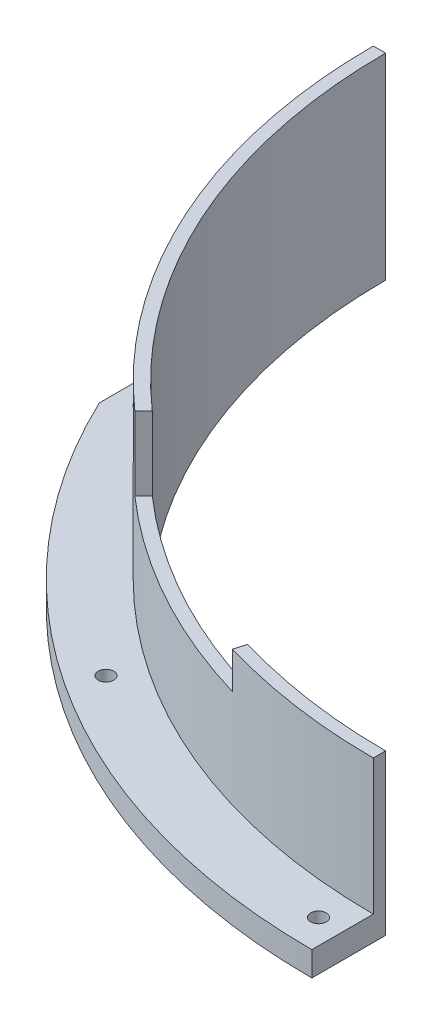
SolidWorks part; units mm, degrees
material "PET"
ref_plane "Front" through (0, 0, 0) normal (0, 0, 1) x (1, 0, 0)
ref_plane "Top" through (0, 0, 0) normal (0, 1, 0) x (1, 0, 0)
ref_plane "Right" through (0, 0, 0) normal (1, 0, 0) x (0, 0, -1)
sketch "Sketch1" plane through (0, 0, 0) normal (0, 1, 0) x (1, 0, 0)
  line L0 (165.608, 0) -> (146.558, 0)
  line L1 (0, -165.608) -> (0, -146.558)
  arc A0 (0, -165.608) -> (165.608, 0) centre (0, 0) ccw
  arc A1 (0, -146.558) -> (146.558, 0) centre (0, 0) ccw
  dimension "D1" = 146.558
  dimension "D2" = 19.05
extrude "Boss-Extrude1" add sketch "Sketch1" along normal blind 6.35
sketch "Sketch2" plane through (0, 6.35, 0) normal (0, 1, 0) x (1, 0, 0)
  line L0 (165.608, 0) -> (146.558, 0) construction
  line L2 (146.558, 0) -> (149.733, 0)
  line L3 (0, -146.558) -> (0, -149.733)
  arc A0 (0, -146.558) -> (146.558, 0) centre (0, 0) ccw
  arc A1 (0, -149.733) -> (149.733, 0) centre (0, 0) ccw
  dimension "D1" = 3.175
extrude "Boss-Extrude2" add sketch "Sketch2" along normal blind 44.45
sketch "Sketch3" plane through (0, 50.8, 0) normal (0, 1, 0) x (1, 0, 0)
  line L0 (96.6779, -110.1483) -> (98.9276, -112.398)
  line L1 (0, -146.558) -> (0, -149.733)
  line L2 (103.6322, -103.6322) -> (105.8772, -105.8772) construction
  arc A0 (0, -146.558) -> (146.558, 0) centre (0, 0) ccw construction
  arc A1 (0, -149.733) -> (149.733, 0) centre (0, 0) ccw construction
  arc A2 (98.9276, -112.398) -> (0, -149.733) centre (0, 0) cw
  arc A3 (0, -146.558) -> (96.6779, -110.1483) centre (0, 0) ccw
  arc A4 (0, -149.733) -> (149.733, 0) centre (0, 0) ccw construction
  dimension "D1" = 9.525
extrude "Cut-Extrude1" cut sketch "Sketch3" against normal blind 9.525
sketch "Sketch4" plane through (0, 41.275, 0) normal (0, 1, 0) x (1, 0, 0)
  line L0 (96.6779, -110.1483) -> (98.9276, -112.398)
  line L1 (98.9276, -112.398) -> (96.6779, -110.1483) construction
  line L2 (41.6294, -140.5213) -> (42.5313, -143.5655)
  line L4 (51.6534, -137.1538) -> (52.8691, -140.0886) construction
  arc A0 (0, -146.558) -> (96.6779, -110.1483) centre (0, 0) ccw construction
  arc A2 (98.9276, -112.398) -> (42.5313, -143.5655) centre (0, 0) cw
  arc A3 (0, -149.733) -> (98.9276, -112.398) centre (0, 0) ccw construction
  arc A4 (96.6779, -110.1483) -> (41.6294, -140.5213) centre (0, 0) cw
  dimension "D1" = 6
extrude "Cut-Extrude2" cut sketch "Sketch4" against normal blind 9.525
sketch "Sketch5" plane through (0, 6.35, 0) normal (0, 1, 0) x (1, 0, 0)
  line L1 (149.733, 0) -> (165.608, 0)
  line L2 (149.733, 0) -> (149.733, -76.2)
  line L3 (149.733, -76.2) -> (165.608, -76.2)
  line L4 (165.608, 0) -> (165.608, -76.2)
  dimension "D1" = 76.2
extrude "Cut-Extrude3" cut sketch "Sketch5" against normal through all
sketch "Sketch8" plane through (0, 6.35, 0) normal (0, 1, 0) x (1, 0, 0)
  line L0 (0, -149.733) -> (0, -165.608) construction
  line L1 (6.35, -157.5426) -> (87.8583, -130.9233) construction
  line L2 (87.8583, -130.9233) -> (143.383, -65.5843) construction
  line L4 (149.733, 0) -> (149.733, -70.7534) construction
  circle A0 centre (0, 0) radius 157.6705 construction
  point P0 (6.35, -157.5426)
  point P2 (87.8583, -130.9233)
  point P4 (143.383, -65.5843)
  point P13 (0, -157.6705)
  dimension "D1" = 6.35
  dimension "D2" = 6.35
hole_wizard "#10-32 Tapped Hole1" positions "Sketch8" profile "Sketch7" tap size "#10-32" standard "ANSI Inch" end condition up to next
sketch "Sketch7" plane through (6.35, 6.35, 157.5426) normal (1, 0, 0) x (0, 0, 1)
  line L0 (0, 0) -> (0, 6.35)
  line L1 (0, 6.35) -> (2.0193, 6.35)
  line L2 (2.0193, 6.35) -> (2.0193, 0)
  line L5 (2.0193, 0) -> (0, 0)
  line L11 (0, -6.35) -> (0, 107.95) construction
  dimension "Thru Tap Drill Dia." = 4.0386
  dimension "Thru Tap Drill Depth" = 6.35
cosmetic thread "Hole Thread1" parameters "D2"=4.826
cosmetic thread "Hole Thread2" parameters "D2"=4.826
cosmetic thread "Hole Thread3" parameters "D2"=4.826
mirror "Mirror1" about plane through (149.733, 0, 0) normal (-1, 0, 0) of bodies 113
cosmetic thread "Hole Thread4" parameters "D2"=4.826
cosmetic thread "Hole Thread5" parameters "D2"=4.826
cosmetic thread "Hole Thread6" parameters "D2"=4.826
delete or keep bodies "Body-Delete/Keep 1" type keep bodies bodies 114
